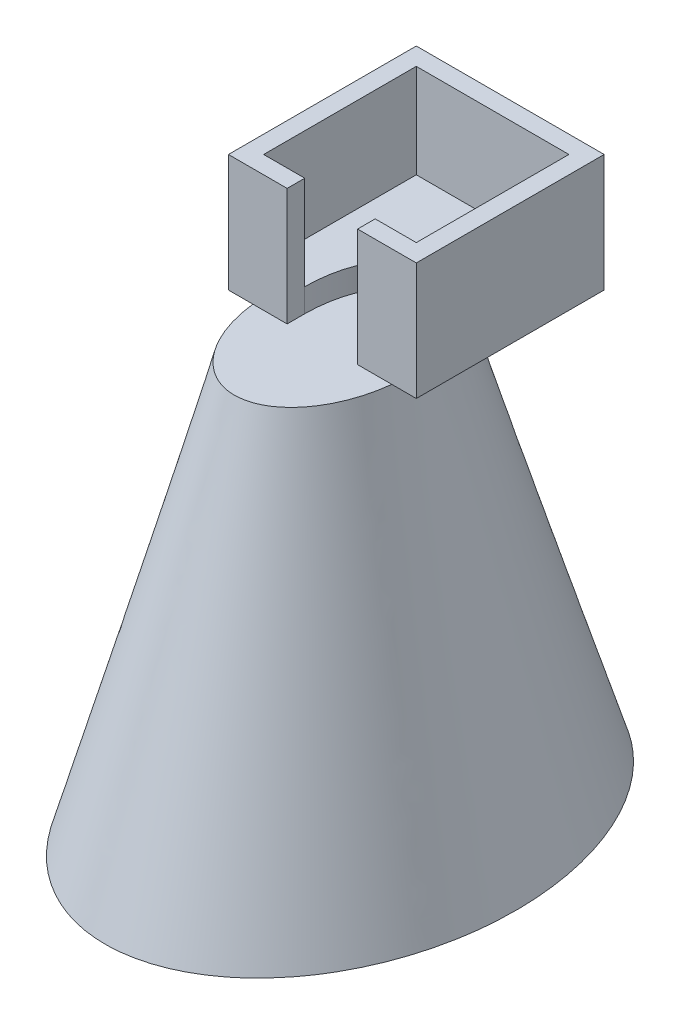
SolidWorks part; units mm, degrees
ref_plane "Plan de face" through (0, 0, 0) normal (0, 0, 1) x (1, 0, 0)
ref_plane "Plan de dessus" through (0, 0, 0) normal (0, 1, 0) x (1, 0, 0)
ref_plane "Plan de droite" through (0, 0, 0) normal (1, 0, 0) x (0, 0, -1)
sketch "Esquisse1" plane through (0, 0, 0) normal (0, 1, 0) x (1, 0, 0)
  line L1 (-8, 8) -> (8, 8)
  line L2 (-8, 8) -> (-8, -8)
  line L3 (-8, -8) -> (8, -8)
  line L4 (8, 8) -> (8, -8)
  line L5 (-8, 8) -> (8, -8) construction
  line L6 (-8, -8) -> (8, 8) construction
  point P0 (0, 0)
  dimension "D1" = 16
  dimension "D2" = 16
extrude "Boss.-Extru.1" add sketch "Esquisse1" along normal blind 10
sketch "Esquisse2" plane through (0, 10, 0) normal (0, 1, 0) x (1, 0, 0)
  line L1 (-6.5, 6.5) -> (6.5, 6.5)
  line L2 (-6.5, 6.5) -> (-6.5, -6.5)
  line L3 (-6.5, -6.5) -> (6.5, -6.5)
  line L4 (6.5, 6.5) -> (6.5, -6.5)
  line L5 (-6.5, 6.5) -> (6.5, -6.5) construction
  line L6 (-6.5, -6.5) -> (6.5, 6.5) construction
  point P0 (0, 0)
  dimension "D1" = 13
  dimension "D2" = 13
extrude "Enlèv. mat.-Extru.1" cut sketch "Esquisse2" against normal blind 8
sketch "Esquisse3" plane through (0, 0, 0) normal (0, 1, 0) x (1, 0, 0)
  line L0 (-8, -8) -> (-3, -8)
  line L1 (-8, -8) -> (8, -8) construction
  line L2 (8, -8) -> (3, -8)
  line L3 (0, 0) -> (0, -8) construction
  line L5 (-6.5, -6.5) -> (6.5, -6.5) construction
  line L6 (-3, -8) -> (3, -8)
  line L7 (-3, -8) -> (-3, -6.5)
  line L8 (-3, -6.5) -> (3, -6.5)
  line L9 (3, -8) -> (3, -6.5)
  line L10 (-8, 8) -> (-8, -8) construction
  line L11 (-6.5, 6.5) -> (-6.5, -6.5) construction
  point P11 (0, -0.5)
  dimension "D1" = 5
  dimension "D2" = 5
  dimension "D3" = 7.5
  dimension "D4" = 1.5
extrude "Enlèv. mat.-Extru.2" cut sketch "Esquisse3" along normal blind 20 contours L8 L3 L6 L9 | L3 L8 L7 L6 region at (1.5, 0, 7.25) region at (-1.5, 0, 7.25)
sketch "Esquisse4" plane through (0, 0, 0) normal (0, -1, 0) x (-1, 0, 0)
  line L0 (0, -6.5) -> (0, -0.5) construction
  line L1 (3, -6.5) -> (-3, -6.5) construction
  ellipse E0 centre (0, -6.5) end of major axis (0, -12.5) minor radius 3
  point P5 (3, -6.5)
  point P6 (-3, -6.5)
  point P7 (-3, -6.5)
  dimension "D1" = 6
extrude "Enlèv. mat.-Extru.4" cut sketch "Esquisse4" against normal blind 20
sketch "Esquisse6" plane through (0, 0, 0) normal (0, -1, 0) x (-1, 0, 0)
  line L0 (3, -6.5) -> (-3, -6.5) construction
  line L1 (0, -0.5) -> (0, 2.5) construction
  ellipse E0 centre (0, -6.5) end of major axis (0, -15.5) minor radius 6
  ellipse E1 centre (0, -6.5) end of major axis (0, -12.5) minor radius 3 (3, -6.5) -> (-3, -6.5) ccw construction
  dimension "D1" = 3
  dimension "D2" = 3
ref_plane "Plan1" through (0, -35, 0) normal (0, 1, 0) x (1, 0, 0)
sketch "Esquisse7" plane through (0, -35, 0) normal (0, 1, 0) x (1, 0, 0)
  line L0 (0, -6.5) -> (0, 13.5) construction
  ellipse E0 centre (0, -6.5) end of major axis (0, 13.5) minor radius 15
  point P4 (0, 3.5)
  dimension "D1" = 20
  dimension "D2" = 1
loft "Lissage1" add profiles "Esquisse7", "Esquisse6" connector at (-9.6482, -35, -8.8137) connector at (-4.994, 0, 1.5116)
